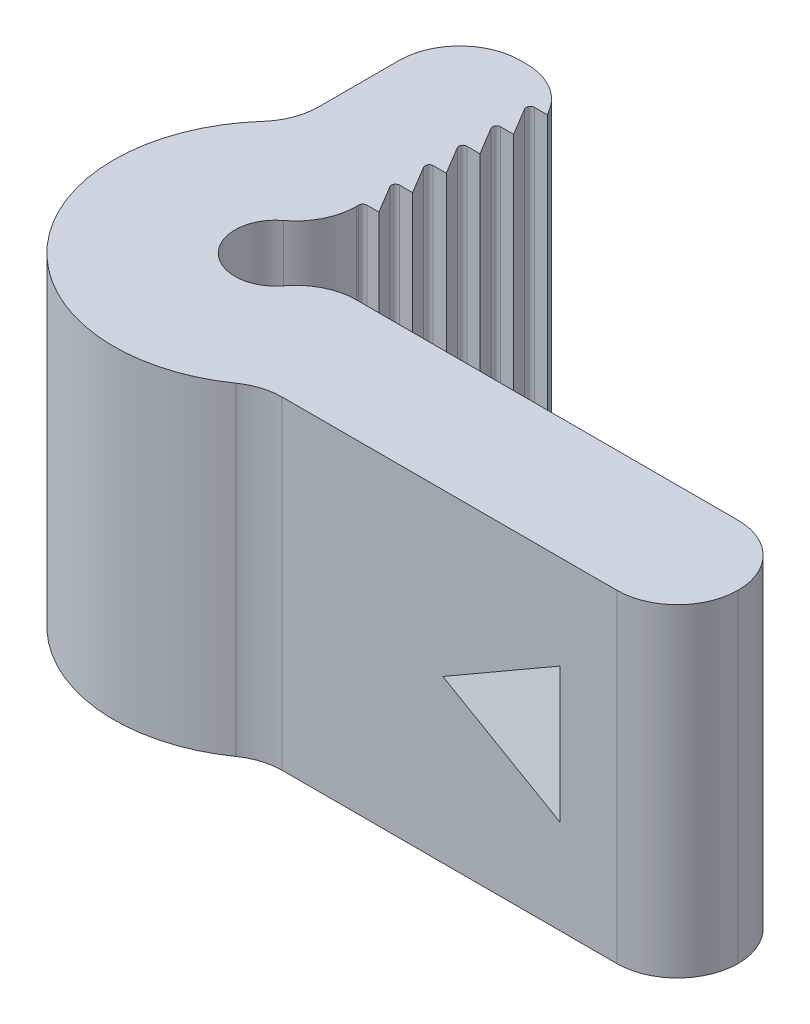
SolidWorks part; units mm, degrees
ref_plane "Front" through (0, 0, 0) normal (0, 0, 1) x (1, 0, 0)
ref_plane "Top" through (0, 0, 0) normal (0, 1, 0) x (1, 0, 0)
ref_plane "Right" through (0, 0, 0) normal (1, 0, 0) x (0, 0, -1)
sketch "Sketch1" plane through (0, 0, 0) normal (0, 1, 0) x (1, 0, 0)
  line L0 (0, 50.8) -> (15, 50.8)
  line L1 (15, 50.8) -> (15, 25.8)
  line L2 (15, 25.8) -> (13, 25.8)
  line L3 (13, 25.8) -> (13, 20)
  line L4 (18, 15) -> (77.7335, 15)
  line L5 (77.7335, 15) -> (77.7335, 0)
  line L9 (13, -5) -> (13, 10) construction
  line L10 (77.7335, 0) -> (26.2288, 0)
  line L11 (0, 50.8) -> (0, 30.1987)
  arc A0 (13, 20) -> (18, 15) centre (13, 15) ccw
  arc A1 (0, 30.1987) -> (26.2288, 0) centre (13, 15) ccw
  dimension "D1" = 5
  dimension "D2" = 64.7335
  dimension "D3" = 10.8
  dimension "D4" = 15
  dimension "D5" = 2
  dimension "D6" = 35.8
extrude "Boss-Extrude1" add sketch "Sketch1" along normal mid plane 40
sketch "Sketch2" plane through (0, 0, -15) normal (0, 0, -1) x (-1, 0, 0)
  line L0 (-48.7106, 0) -> (-63.1732, 8.35)
  line L1 (-63.1732, 8.35) -> (-63.1732, -8.35)
  line L2 (-63.1732, -8.35) -> (-48.7106, 0)
  line L3 (-77.7335, 20) -> (-77.7335, -20) construction
  line L5 (-15, 20) -> (-15, -20) construction
  point P5 (-63.1732, 0)
  point P6 (-77.7335, 0)
  dimension "D1" = 16.7
  dimension "D2" = 33.7106
extrude "Cut-Extrude1" cut sketch "Sketch2" against normal through all
sketch "Sketch3" plane through (0, 20, 0) normal (0, 1, 0) x (1, 0, 0)
  line L0 (15, 25.8) -> (12.5, 29.9667)
  line L1 (12.5, 29.9667) -> (15, 29.9667)
  line L3 (15, 25.8) -> (15, 50.8) construction
  line L4 (15, 29.9667) -> (15, 25.8)
  line L5 (15, 29.9667) -> (15, 34.1333) construction
  line L6 (15, 34.1333) -> (15, 38.3) construction
  line L7 (15, 38.3) -> (15, 42.4667) construction
  line L8 (15, 42.4667) -> (15, 46.6333) construction
  line L9 (15, 46.6333) -> (15, 50.8) construction
  dimension "D1" = 2.5
extrude "Cut-Extrude2" cut sketch "Sketch3" against normal through all
pattern_linear "LPattern1" count 6 spacing 4.1667 along (0, 0, -1) of "Cut-Extrude2"
fillet "Fillet1" radius 0.5 6 edges at (13, 0, -25.8) (12.5, 0, -29.9667) (12.5, 0, -46.6333) (12.5, 0, -42.4667) (12.5, 0, -38.3) (12.5, 0, -34.1333)
fillet "Fillet2" radius 7.5 8 edges at (12.5, 0, -50.8) (77.7335, 0, -15) (77.7335, 0, 0) (26.2288, 0, 0) (0, 0, -30.1987) (0, 0, -50.8) (13, 0, -20) (18, 0, -15)
